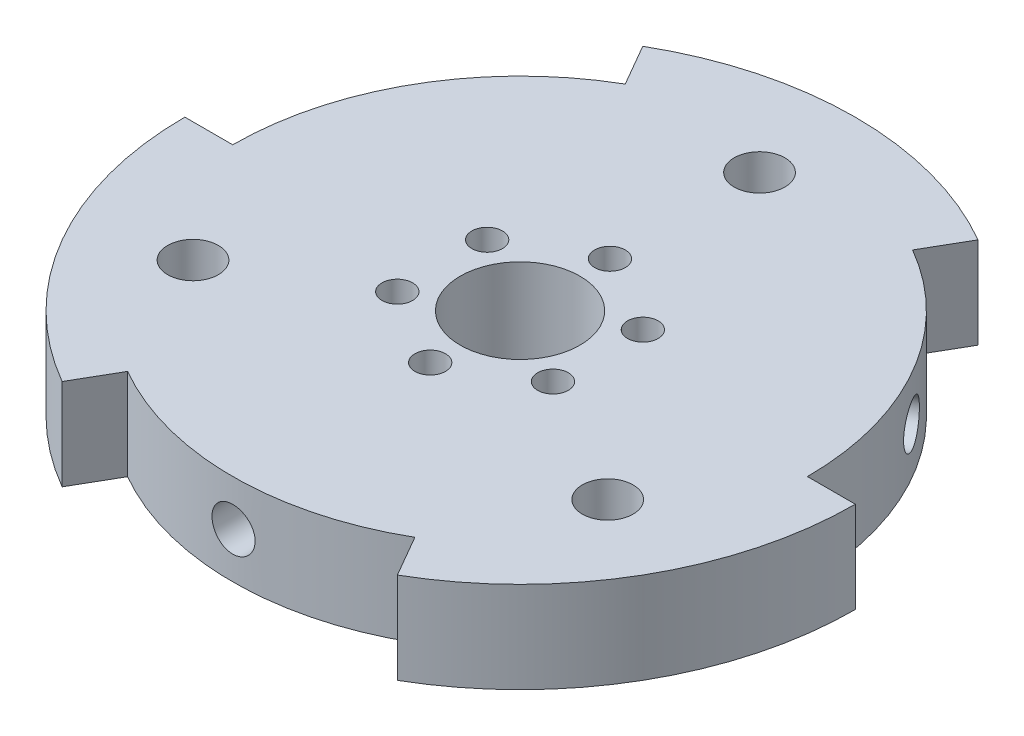
SolidWorks part; units mm, degrees
ref_plane "Front Plane" through (0, 0, 0) normal (0, 0, 1) x (1, 0, 0)
ref_plane "Top Plane" through (0, 0, 0) normal (0, 1, 0) x (1, 0, 0)
ref_plane "Right Plane" through (0, 0, 0) normal (1, 0, 0) x (0, 0, -1)
sketch "Baseplate Sketch" plane through (0, 0, 0) normal (0, 1, 0) x (1, 0, 0)
  line L0 (0, 0) -> (0, 61.4504) construction
  line L1 (-17.5, 30.3109) -> (-15, 25.9808)
  line L2 (17.5, 30.3109) -> (15, 25.9808)
  line L3 (-17.5, 30.3109) -> (-21.8301, 27.8109) construction
  line L4 (17.5, 30.3109) -> (13.1699, 32.8109) construction
  line L5 (17.5, -30.3109) -> (15, -25.9808)
  line L6 (35, 0) -> (30, 0)
  line L7 (-35, 0) -> (-30, 0)
  line L8 (-17.5, -30.3109) -> (-15, -25.9808)
  circle A0 centre (0, 0) radius 30
  circle A1 centre (0, 0) radius 6.25
  arc A2 (-17.5, 30.3109) -> (17.5, 30.3109) centre (0, 0) cw
  arc A3 (35, 0) -> (17.5, -30.3109) centre (0, 0) cw
  arc A4 (-17.5, -30.3109) -> (-35, 0) centre (0, 0) cw
  circle A5 centre (0, 25) radius 2.65
  circle A6 centre (21.6506, -12.5) radius 2.65
  circle A7 centre (-21.6506, -12.5) radius 2.65
  point P15 (0, 35)
  point P25 (0, 0)
  point P31 (0, 0)
  dimension "D1" = 60
  dimension "D2" = 12.5
  dimension "D3" = 35
  dimension "D4" = 90
  dimension "D5" = 5
  dimension "D12" = 5.3
  dimension "D6" = 5
  dimension "D7" = 90
  dimension "D8" = 60
  dimension "D9" = 5
  dimension "D10" = 5
  dimension "D14" = 25
  dimension "D11" = 3
  dimension "D13" = 3
extrude "Boss-Extrude1" add sketch "Baseplate Sketch" along normal blind 9.525 contours A4 L8 A0 L7 | A3 L6 A0 L5 | A2 L1 A0 L2 | A0 | A1 | A6 | A7 | A5 region at (0, 0, -31.0964) region at (-26.9303, 0, 15.5482) region at (26.9303, 0, 15.5482)
ref_plane "Plane1" through (0, 0, 40) normal (0, 0, 1) x (1, 0, 0)
sketch "Sketch2" plane through (0, 0, 40) normal (0, 0, 1) x (1, 0, 0)
  line L0 (0, 9.525) -> (0, 0) construction
  line L4 (15, 9.525) -> (-15, 9.525)
  line L5 (-15, 9.525) -> (-15, 0)
  line L6 (-15, 0) -> (15, 0)
  line L7 (15, 0) -> (15, 9.525)
  line L8 (15, 9.525) -> (-15, 9.525) construction
  line L9 (-15, 9.525) -> (-15, 0) construction
  line L10 (-15, 0) -> (15, 0) construction
  line L11 (15, 0) -> (15, 9.525) construction
  circle A0 centre (0, 4.7625) radius 2.25
  dimension "D1" = 0
  dimension "D2" = 4.5
extrude "Cut-Extrude1" cut sketch "Sketch2" against normal blind 25
pattern_circular "CirPattern1" count 3 over 360 about axis through (0, 9.525, 0) along (0, 1, 0) of "Cut-Extrude1"
sketch "Sketch3" plane through (0, 9.525, 0) normal (0, 1, 0) x (1, 0, 0)
  circle A2 centre (-8.1276, -4.6925) radius 1.6
  circle A5 centre (0, -9.385) radius 1.6
  circle A6 centre (-8.1276, 4.6925) radius 1.6
  circle A7 centre (0, 9.385) radius 1.6
  circle A8 centre (8.1276, 4.6925) radius 1.6
  circle A9 centre (8.1276, -4.6925) radius 1.6
  point P3 (0, 0)
  point P14 (0, 0)
  dimension "D1" = 3.2
  dimension "D2" = 9.385
  dimension "D3" = 9.385
extrude "Cut-Extrude2" cut sketch "Sketch3" against normal up to surface (9.525 mm away) contours A5 | A2 | A6 | A7 | A8 | A9 region at (-8.1276, 9.525, 4.6925) region at (0, 9.525, 9.385) region at (-8.1276, 9.525, -4.6925) region at (0, 9.525, -9.385) region at (8.1276, 9.525, -4.6925) region at (8.1276, 9.525, 4.6925) up to face at (0, 0, 0)
